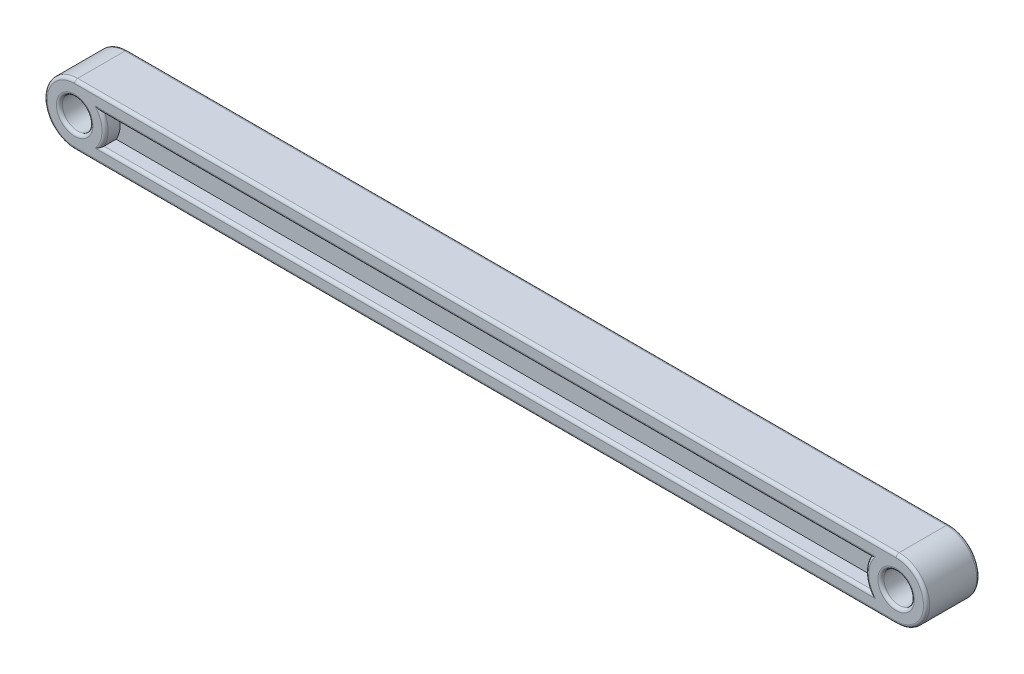
SolidWorks part; units mm, degrees
ref_plane "Front Plane" through (0, 0, 0) normal (0, 0, 1) x (1, 0, 0)
ref_plane "Top Plane" through (0, 0, 0) normal (0, 1, 0) x (1, 0, 0)
ref_plane "Right Plane" through (0, 0, 0) normal (1, 0, 0) x (0, 0, -1)
sketch "Sketch2" plane through (0, 0, 0) normal (0, 0, 1) x (1, 0, 0)
  line L0 (-270, 0) -> (270, 0) construction
  line L1 (-270, 20) -> (270, 20)
  line L2 (-270, -20) -> (270, -20)
  arc A0 (-270, 20) -> (-270, -20) centre (-270, 0) ccw
  arc A1 (270, -20) -> (270, 20) centre (270, 0) ccw
  circle A2 centre (-270, 0) radius 10
  circle A3 centre (270, 0) radius 10
  point P3 (0, 0)
  dimension "D1" = 580
  dimension "D2" = 20
  dimension "D3" = 20
extrude "Boss-Extrude1" add sketch "Sketch2" along normal mid plane 35
sketch "Sketch4" plane through (0, 0, -17.5) normal (0, 0, -1) x (-1, 0, 0)
  line L4 (270, 10) -> (-270, 10)
  line L5 (-270, -10) -> (270, -10)
  line L6 (252.6795, 10) -> (-252.6795, 10)
  line L7 (-252.6795, -10) -> (252.6795, -10)
  arc A4 (270, -10) -> (270, 10) centre (270, 0) ccw
  arc A5 (-270, 10) -> (-270, -10) centre (-270, 0) ccw
  circle A8 centre (-270, 0) radius 20
  arc A9 (-252.6795, -10) -> (-252.6795, 10) centre (-270, 0) ccw
  circle A11 centre (270, 0) radius 20
  arc A12 (252.6795, 10) -> (252.6795, -10) centre (270, 0) ccw
  dimension "D1" = 10
  dimension "D2" = 10
  dimension "D3" = 10
extrude "Cut-Extrude1" cut sketch "Sketch4" against normal blind 10
mirror "Mirror1" about plane through (0, 0, 0) normal (0, 0, 1) of "Cut-Extrude1"
fillet "Fillet4" radius 2 20 edges at (280, 0, -17.5) (280, 0, 17.5) (-260, 0, -17.5) (-260, 0, 17.5) (0, -10, 17.5) (-250, 0, 17.5) (0, 10, 17.5) (250, 0, 17.5) (-250, 0, -17.5) (0, -10, -17.5) (250, 0, -17.5) (0, 10, -17.5) (0, 20, 17.5) (290, 0, 17.5) (0, -20, 17.5) (-290, 0, 17.5) (0, -20, -17.5) (290, 0, -17.5) (0, 20, -17.5) (-290, 0, -17.5)
